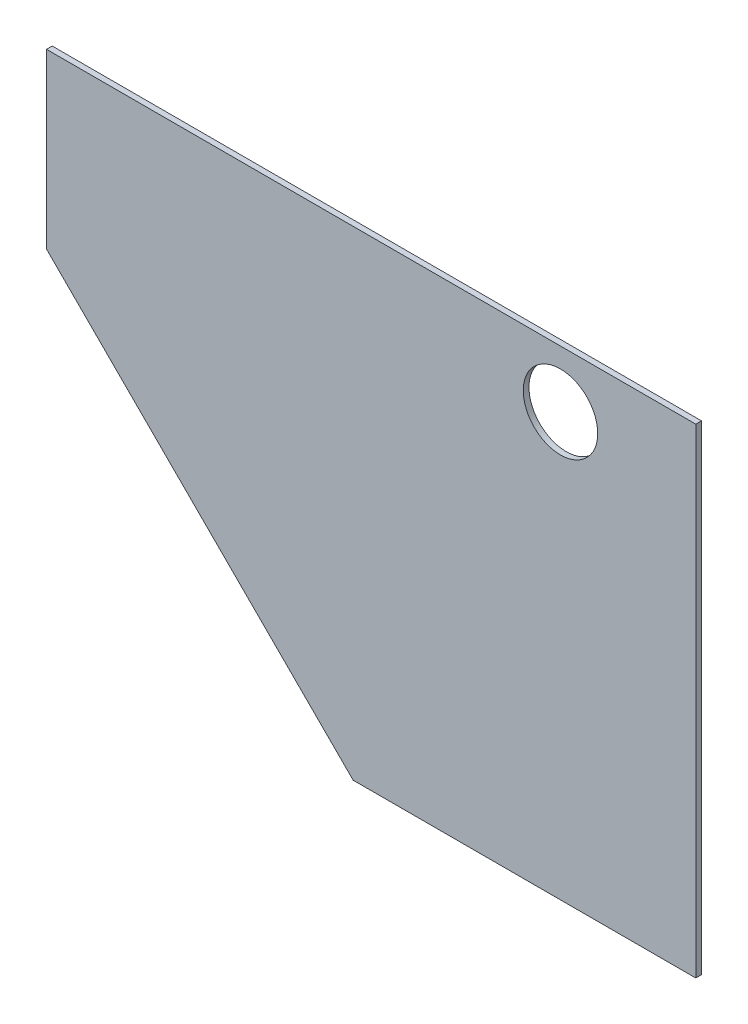
SolidWorks part; units mm, degrees
ref_plane "Front Plane" through (0, 0, 0) normal (0, 0, 1) x (1, 0, 0)
ref_plane "Top Plane" through (0, 0, 0) normal (0, 1, 0) x (1, 0, 0)
ref_plane "Right Plane" through (0, 0, 0) normal (1, 0, 0) x (0, 0, -1)
sketch "Sketch1" plane through (0, 0, 0) normal (0, 0, 1) x (1, 0, 0)
  line L0 (-138.2594, 48.9915) -> (32.2106, -121.4785)
  line L1 (32.2106, -121.4785) -> (222.7106, -121.4785)
  line L2 (-138.2594, 145.2215) -> (-138.2594, 48.9915)
  line L3 (-138.2594, 145.2215) -> (222.7106, 145.2215)
  line L4 (222.7106, -121.4785) -> (222.7106, 145.2215)
  circle A0 centre (147.4906, 113.4715) radius 20.701
  circle A2 centre (147.4906, 113.4715) radius 69.85 construction
  circle A3 centre (147.4906, 113.4715) radius 285.75 construction
  point P0 (0, 0)
  point P2 (147.4906, 113.4715)
  dimension "D4" = 234.95
  dimension "D1" = 45
  dimension "D2" = 266.7
  dimension "D5" = 247.65
extrude "Boss-Extrude1" add sketch "Sketch1" along normal blind 3.175
